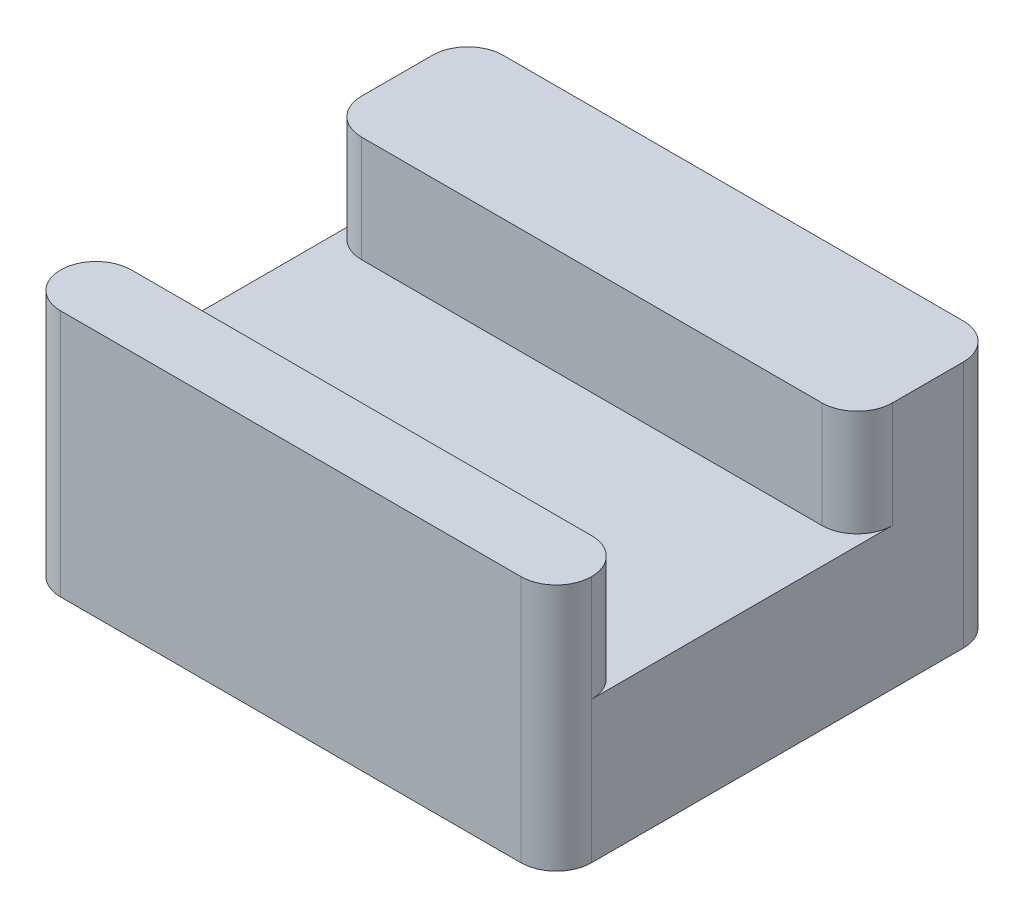
SolidWorks part; units mm, degrees
ref_plane "Front Plane" through (0, 0, 0) normal (0, 0, 1) x (1, 0, 0)
ref_plane "Top Plane" through (0, 0, 0) normal (0, 1, 0) x (1, 0, 0)
ref_plane "Right Plane" through (0, 0, 0) normal (1, 0, 0) x (0, 0, -1)
sketch "Sketch1" plane through (0, 0, 0) normal (0, 1, 0) x (1, 0, 0)
  line L1 (-7.5, -6.25) -> (7.5, -6.25)
  line L2 (-7.5, -6.25) -> (-7.5, 6.25)
  line L3 (-7.5, 6.25) -> (7.5, 6.25)
  line L4 (7.5, -6.25) -> (7.5, 6.25)
  line L5 (-7.5, -6.25) -> (7.5, 6.25) construction
  line L6 (-7.5, 6.25) -> (7.5, -6.25) construction
  point P0 (0, 0)
  dimension "D1" = 15
  dimension "D2" = 12.5
extrude "Boss-Extrude1" add sketch "Sketch1" along normal blind 7
sketch "Sketch2" plane through (0, 7, 0) normal (0, 1, 0) x (1, 0, 0)
  line L0 (-7.5, -6.25) -> (7.5, -6.25) construction
  line L1 (-7.5, -4.25) -> (7.5, -4.25)
  line L2 (-7.5, -4.25) -> (-7.5, 2.25)
  line L3 (-7.5, 2.25) -> (7.5, 2.25)
  line L4 (7.5, -4.25) -> (7.5, 2.25)
  line L5 (-7.5, -4.25) -> (7.5, 2.25) construction
  line L6 (-7.5, 2.25) -> (7.5, -4.25) construction
  line L7 (-7.5, 6.25) -> (-7.5, -6.25) construction
  line L8 (7.5, -6.25) -> (7.5, 6.25) construction
  point P0 (0, -1)
  dimension "D1" = 2
  dimension "D2" = 6.5
extrude "Cut-Extrude2" cut sketch "Sketch2" against normal blind 3
sketch "Sketch3" plane through (0, 0, -6.25) normal (0, 0, -1) x (-1, 0, 0)
  line L0 (-7.5, 0) -> (7.5, 0) construction
  line L1 (0, 3.85) -> (0, -3.85) construction
  circle A0 centre (0, 2) radius 1.3
  dimension "D1" = 2.6
  dimension "D2" = 2
extrude "Cut-Extrude3" cut sketch "Sketch3" against normal blind 10.5
fillet "Fillet1" radius 1 8 edges at (-7.5, 3.5, 6.25) (-7.5, 5.5, 4.25) (-7.5, 5.5, -2.25) (-7.5, 3.5, -6.25) (7.5, 3.5, -6.25) (7.5, 5.5, -2.25) (7.5, 5.5, 4.25) (7.5, 3.5, 6.25)
